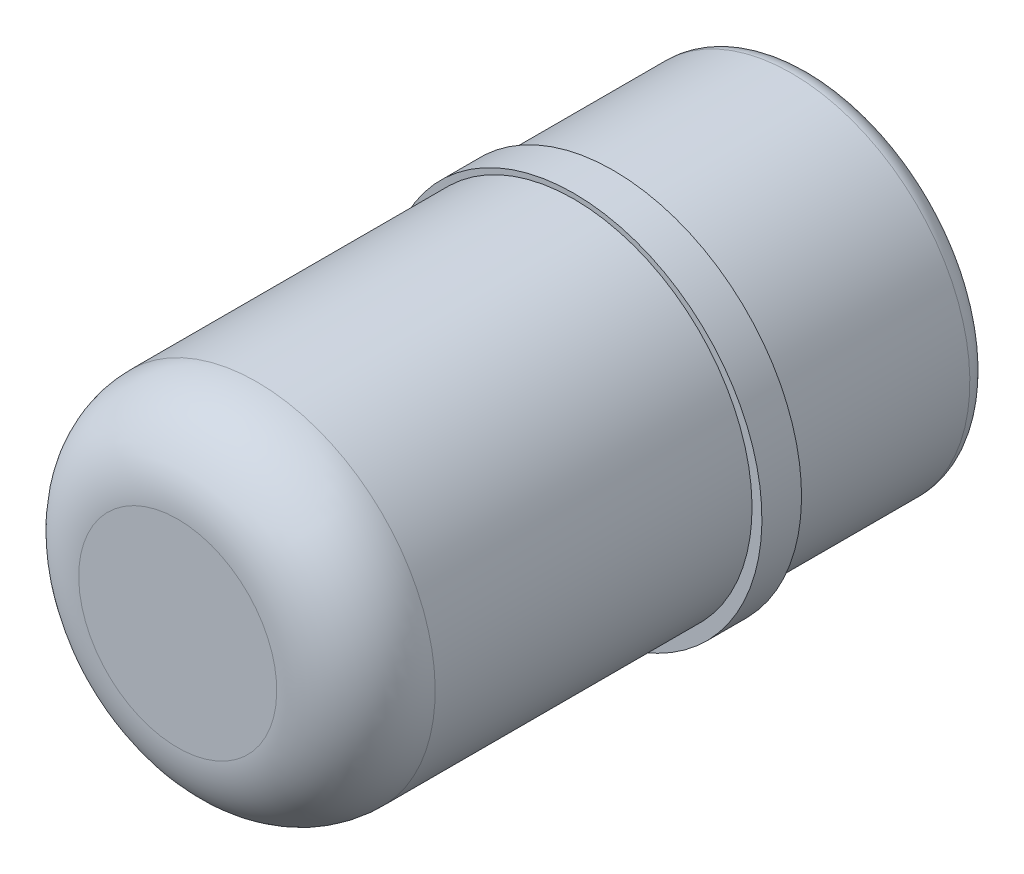
SolidWorks part; units mm, degrees
material "PET"
ref_plane "Front Plane" through (0, 0, 0) normal (1, 0, 0) x (0, 1, 0)
ref_plane "Top Plane" through (0, 0, 0) normal (0, 0, 1) x (0, 1, 0)
ref_plane "Right Plane" through (0, 0, 0) normal (0, 1, 0) x (-1, 0, 0)
sketch "Sketch1" plane through (0, 0, 0) normal (1, 0, 0) x (0, 1, 0)
  line L1 (-23.75, -5) -> (23.75, -5)
  line L2 (-23.75, -5) -> (-23.75, 5)
  line L3 (-23.75, 5) -> (23.75, 5)
  line L4 (23.75, -5) -> (23.75, 5)
  line L5 (-23.75, -5) -> (23.75, 5) construction
  line L6 (-23.75, 5) -> (23.75, -5) construction
  line L7 (-22.5, -55) -> (22.5, -55)
  line L8 (-22.5, -55) -> (-22.5, -5)
  line L9 (-22.5, -5) -> (22.5, -5)
  line L10 (22.5, -55) -> (22.5, -5)
  line L11 (-22.5, -55) -> (22.5, -5) construction
  line L12 (-22.5, -5) -> (22.5, -55) construction
  line L13 (-22.5, 5) -> (22.5, 5)
  line L14 (-22.5, 5) -> (-22.5, 105)
  line L15 (-22.5, 105) -> (22.5, 105)
  line L16 (22.5, 5) -> (22.5, 105)
  line L17 (-22.5, 5) -> (22.5, 105) construction
  line L18 (-22.5, 105) -> (22.5, 5) construction
  point P0 (0, 0)
  point P5 (0, -30)
  point P11 (0, -5)
  point P12 (0, -5)
  point P13 (0, 55)
  point P18 (0, 5)
  point P19 (0, 5)
  dimension "D1" = 100
  dimension "D2" = 10
  dimension "D3" = 45
  dimension "D4" = 45
  dimension "D5" = 50
  dimension "D6" = 47.5
revolve "Revolve2" add sketch "Sketch1" angle 360 about L14 region at (0, 0, 55)
revolve "Revolve3" add sketch "Sketch1<6>" angle 360 about L2 region at (0, 0, 0)
sketch "Sketch1<6>" plane through (0, 0, 0) normal (1, 0, 0) x (0, 1, 0) same geometry as "Sketch1"
revolve "Revolve4" add sketch "Sketch1<7>" angle 360 about L8 region at (0, 0, -30)
sketch "Sketch1<7>" plane through (0, 0, 0) normal (1, 0, 0) x (0, 1, 0) same geometry as "Sketch1"
fillet "Fillet1" radius 20 1 edges at (0, 22.5, 105)
fillet "Fillet2" radius 5 1 edges at (0, 22.5, -55)
